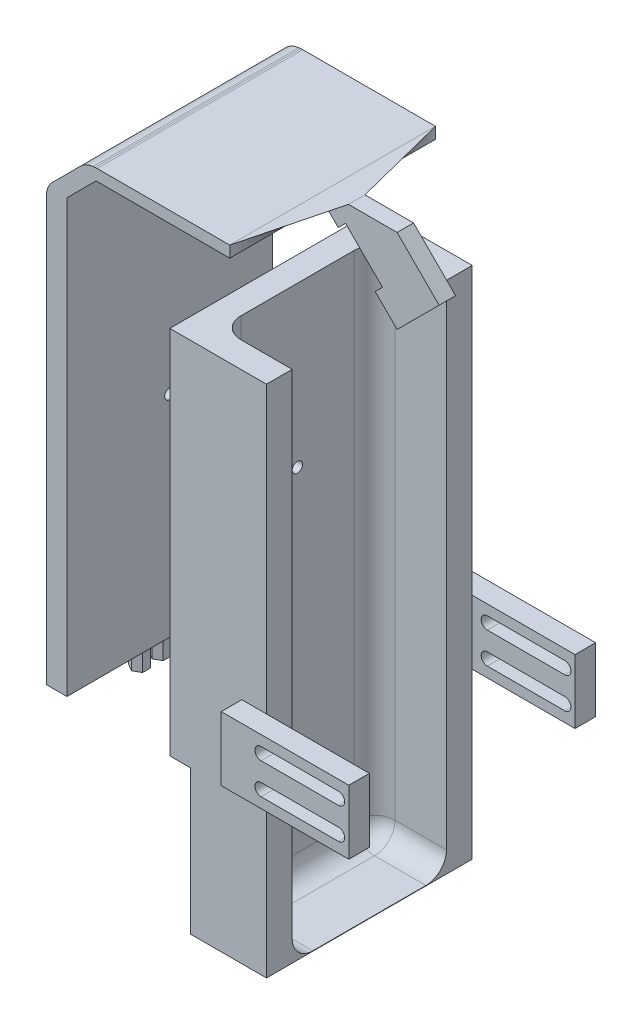
SolidWorks part; units mm, degrees
note: '?' marks a value the reader was unsure of.
ref_plane "Front Plane" through (0, 0, 0) normal (0, 0, 1) x (1, 0, 0)
ref_plane "Top Plane" through (0, 0, 0) normal (0, 1, 0) x (1, 0, 0)
ref_plane "Right Plane" through (0, 0, 0) normal (1, 0, 0) x (0, 0, -1)
sketch "Sketch1" plane through (0, 0, 0) normal (0, 1, 0) x (1, 0, 0)
  line L1 (0, 0) -> (25, 0)
  line L2 (0, 0) -> (0, 100)
  line L3 (0, 100) -> (25, 100)
  line L4 (25, 0) -> (25, 100)
  dimension "D1" = 100
  dimension "D2" = 25
extrude "Boss-Extrude1" add sketch "Sketch1" along normal blind 250
ref_plane "Plane1" through (35, 0, 0) normal (1, 0, 0) x (0, 0, -1)
ref_axis "Axis1" through (25, 250, 291.9882) along (0, 0, -1)?
ref_plane "Plane2" through (137.5, 137.5, 0) normal (-0.7071, -0.7071, 0) x (0, 0, -1)
sketch "Sketch5" plane through (0, 250, 0) normal (0, 1, 0) x (1, 0, 0)
  line L0 (0, 0) -> (-50, 0) construction
  line L2 (-50, 0) -> (-60, 0)
  line L3 (-50, 0) -> (-50, 100)
  line L4 (-50, 100) -> (-60, 100)
  line L5 (-60, 0) -> (-60, 100)
  dimension "D1" = 10
  dimension "D2" = 100
  dimension "D3" = 50
extrude "Boss-Extrude2" add sketch "Sketch5" against normal blind 250 and the other way blind 30 separate body
sketch "Sketch6" plane through (-60, 0, 0) normal (-1, 0, 0) x (0, 0, 1)
  line L0 (-100, 0) -> (-100, 175) construction
  line L1 (-100, 0) -> (-100, 280) construction
  line L2 (0, 0) -> (0, 280) construction
  line L3 (-100, 175) -> (0, 175) construction
  line L4 (-100, 175) -> (-100, 170) construction
  line L5 (-100, 170) -> (0, 170) construction
  line L6 (0, 175) -> (0, 170) construction
  line L7 (-50, 175) -> (-50, 170) construction
  circle A0 centre (-50, 172.5) radius 2.5
  dimension "D1" = 5
  dimension "D2" = 175
extrude "Cut-Extrude1" cut sketch "Sketch6" against normal blind 250
ref_plane "Plane3" through (115, 115, 0) normal (0.7071, 0.7071, 0) x (0, 0, -1)
sketch "Sketch7" plane through (115, 115, 0) normal (0.7071, 0.7071, 0) x (0, 0, -1)
  line L1 (0, 233.3452) -> (100, 233.3452)
  line L2 (0, 233.3452) -> (0, 240.4163)
  line L3 (0, 240.4163) -> (100, 240.4163)
  line L4 (100, 233.3452) -> (100, 240.4163)
extrude "Boss-Extrude3" add sketch "Sketch7" along normal blind 20 separate body
loft "Loft1" add section face at (-55, 280, -50) section face at (-52.5, 282.5, -50)
fillet "Fillet1" radius 10 1 edges
ref_plane "Plane4" through (-35.8579, 0, 0) normal (1, 0, 0) x (0, 0, -1)
sketch "Sketch8" plane through (-35.8579, 0, 0) normal (1, 0, 0) x (0, 0, -1)
  line L1 (100, 294.1421) -> (0, 294.1421)
  line L2 (100, 294.1421) -> (100, 299.6421)
  line L3 (100, 299.6421) -> (0, 299.6421)
  line L4 (0, 294.1421) -> (0, 299.6421)
  dimension "D1" = 5.5
  dimension "D2" = 100
extrude "Boss-Extrude4" add sketch "Sketch8" along normal blind 65 separate body
loft "Loft2" add section face at (-38.3579, 296.6421, -50) section face at (-35.8579, 296.8921, -50)
fillet "Fillet2" radius 10 2 edges
ref_plane "Plane5" through (-132.5, 132.5, 0) normal (0.7071, -0.7071, 0) x (0, 0, -1)
sketch "Sketch9" plane through (-132.5, 132.5, 0) normal (0.7071, -0.7071, 0) x (0, 0, -1)
  line L0 (0, 228.5965) -> (100, 228.5965) construction
  line L5 (46, 232.4856) -> (54, 232.4856) construction
  line L6 (46, 232.4856) -> (54, 232.4856)
  line L7 (46, 232.4856) -> (46, 228.5965)
  line L8 (46, 228.5965) -> (54, 228.5965)
  line L9 (54, 232.4856) -> (54, 228.5965)
  line L10 (100, 232.4856) -> (0, 232.4856) construction
  point P9 (50, 232.4856)
  dimension "D1" = 8
  dimension "D2" = 46
extrude "Boss-Extrude5" add sketch "Sketch9" along normal blind 50 separate body
sketch "Sketch11" plane through (161.6421, 161.6421, 0) normal (-0.7071, -0.7071, 0) x (0, 0, 1)
  line L0 (-46, 137.3833) -> (-46, 162.3833) construction
  line L1 (-46, 137.3833) -> (-46, 187.3833) construction
  line L2 (-54, 137.3833) -> (-54, 187.3833) construction
  line L3 (-46, 162.3833) -> (-54, 162.3833) construction
  line L4 (-46, 162.3833) -> (-46, 167.9142) construction
  line L5 (-46, 167.9142) -> (-54, 167.9142) construction
  line L6 (-54, 162.3833) -> (-54, 167.9142) construction
  line L7 (-50, 167.9142) -> (-50, 162.3833) construction
  line L8 (-54, 165.1488) -> (-46, 165.1488) construction
  line L10 (-62.7, 152.4488) -> (-37.3, 152.4488)
  line L11 (-62.7, 152.4488) -> (-62.7, 177.8488)
  line L12 (-62.7, 177.8488) -> (-37.3, 177.8488)
  line L13 (-37.3, 152.4488) -> (-37.3, 177.8488)
  line L14 (-62.7, 152.4488) -> (-37.3, 177.8488) construction
  line L15 (-62.7, 177.8488) -> (-37.3, 152.4488) construction
  point P14 (-50, 165.1488)
  dimension "D1" = 25.4
  dimension "D2" = 25.4
  dimension "D3" = 9.5345
sketch "Sketch12" plane through (-97.1447, 97.1447, 0) normal (0.7071, -0.7071, 0) x (0, 0, -1)
  line L2 (46, 232.4856) -> (54, 232.4856)
  line L3 (46, 232.4856) -> (46, 257.4856)
  line L4 (46, 257.4856) -> (54, 257.4856)
  line L5 (54, 232.4856) -> (54, 257.4856)
  dimension "D1" = 25
  dimension "D2" = 8
extrude "Boss-Extrude7" add sketch "Sketch12" against normal blind 50
extrude "Cut-Extrude4" cut sketch "Sketch11" against normal blind 5
sketch "Sketch14" plane through (35, 0, 0) normal (1, 0, 0) x (0, 0, -1)
  line L6 (100, 299.6421) -> (0, 299.6421) construction
  line L7 (54, 314.5698) -> (46, 314.5698)
  line L8 (54, 314.5698) -> (54, 299.6421)
  line L9 (54, 299.6421) -> (46, 299.6421)
  line L10 (46, 314.5698) -> (46, 299.6421)
  line L11 (54, 314.5698) -> (46, 314.5698) construction
  dimension "D1" = 8
extrude "Cut-Extrude6" cut sketch "Sketch14" along normal blind 80 and the other way blind 10
sketch "Sketch15" plane through (0, 0, 0) normal (0, 0, 1) x (1, 0, 0)
  line L1 (25, 0) -> (47, 0)
  line L2 (25, 0) -> (25, 250)
  line L3 (25, 250) -> (47, 250)
  line L4 (47, 0) -> (47, 250)
  dimension "D1" = 22
  dimension "D2" = 25
extrude "Boss-Extrude8" add sketch "Sketch15" against normal blind 100
sketch "Sketch16" plane through (47, 0, 0) normal (1, 0, 0) x (0, 0, -1)
  line L0 (0, 0) -> (100, 0) construction
  line L1 (12.5, 0) -> (87.5, 0) construction
  line L2 (100, 250) -> (0, 250) construction
  line L3 (12.5, 0) -> (87.5, 0)
  line L4 (12.5, 0) -> (12.5, 250)
  line L5 (12.5, 250) -> (87.5, 250)
  line L6 (87.5, 0) -> (87.5, 250)
  line L7 (0, 280) -> (0, 0) construction
  point P7 (50, 0)
  dimension "D1" = 12.5
extrude "Cut-Extrude7" cut sketch "Sketch16" against normal blind 35
fillet "Fillet4" radius 10 2 edges at (12, 125, -87.5) (12, 125, -12.5)
sketch "Sketch18" plane through (0, 0, -87.5) normal (0, 0, 1) x (1, 0, 0)
  line L1 (47, 0) -> (12, 0)
  line L2 (47, 0) -> (47, 0.2)
  line L3 (47, 0.2) -> (12, 0.2)
  line L4 (12, 0) -> (12, 0.2)
  dimension "D1" = 35
  dimension "D2" = 0.2
extrude "Boss-Extrude10" add sketch "Sketch18" along normal blind 75
fillet "Fillet5" radius 10 5 edges at (34.5, 0.2, -12.5) (14.9289, 0.2, -15.4289) (34.5, 0.2, -87.5) (14.9289, 0.2, -84.5711) (12, 0.2, -50)
fillet "Fillet6" radius 15 1 edges at (34.6421, 299.6421, -50)
surface "Surface-Loft1"
sketch "Sketch19" plane through (0, 0, 0) normal (0, 0, 1) x (1, 0, 0)
  line L0 (0, 0) -> (0, 80) construction
  line L1 (0, 250) -> (0, 0) construction
  line L2 (0, 80) -> (47, 80) construction
  line L3 (47, 0) -> (47, 250) construction
  line L4 (54.3576, 103.16) -> (92, 103.16) construction
  line L5 (47, 80) -> (97, 80)
  line L7 (47, 111.16) -> (97, 111.16)
  line L8 (97, 80) -> (97, 111.16)
  line L9 (54.3576, 106.16) -> (92, 106.16)
  line L10 (54.3576, 100.16) -> (92, 100.16)
  line L11 (54.3576, 88) -> (92, 88) construction
  line L12 (54.3576, 91) -> (92, 91)
  line L13 (54.3576, 85) -> (92, 85)
  line L14 (92, 106.16) -> (92, 111.16) construction
  line L15 (92, 106.16) -> (97, 111.16)
  line L16 (47, 111.16) -> (35, 111.16)
  line L17 (35, -55.0055) -> (35, 55.0055) construction
  line L18 (35, 111.16) -> (35, 80)
  line L19 (35, 80) -> (47, 80)
  arc A0 (54.3576, 106.16) -> (54.3576, 100.16) centre (54.3576, 103.16) ccw
  arc A1 (92, 100.16) -> (92, 106.16) centre (92, 103.16) ccw
  arc A2 (54.3576, 91) -> (54.3576, 85) centre (54.3576, 88) ccw
  arc A3 (92, 85) -> (92, 91) centre (92, 88) ccw
  point P13 (73.1788, 103.16)
  point P23 (73.1788, 88)
  dimension "D8" = 5
  dimension "D4" = 45
  dimension "D1" = 31.16
  dimension "D2" = 12
  dimension "D3" = 80
  dimension "D5" = 6
  dimension "D7" = 9.16
  dimension "D9" = 37.6424
  dimension "D10" = 50
  dimension "D6" = 2
extrude "Boss-Extrude11" add sketch "Sketch19" against normal blind 110 and the other way blind 10
sketch "Sketch20" plane through (0, 111.16, 0) normal (0, 1, 0) x (1, 0, 0)
  line L5 (97, -10) -> (97, 110) construction
  line L6 (47, 100) -> (97, 100)
  line L8 (47, 0) -> (97, 0)
  line L9 (97, 100) -> (97, 0)
  line L10 (22, 12.5) -> (47, 12.5) construction
  line L11 (34.5, 12.5) -> (47, 12.5)
  line L12 (34.5, 12.5) -> (34.5, 87.5)
  line L13 (34.5, 87.5) -> (47, 87.5)
  line L15 (47, 87.5) -> (35, 87.5) construction
  line L17 (47, 12.5) -> (47, 0)
  line L18 (47, 100) -> (47, 87.5)
  dimension "D1" = 50
  dimension "D2" = 100
extrude "Cut-Extrude8" cut sketch "Sketch20" against normal blind 100
sketch "Sketch21" plane through (0, 0, 0) normal (0, 0, 1) x (1, 0, 0)
  line L0 (0, 0) -> (0, 70) construction
  line L1 (0, 250) -> (0, 0) construction
  line L2 (0, 70) -> (10, 70) construction
  line L3 (0, 0) -> (47, 0) construction
  line L4 (0, 70) -> (10, 70)
  line L5 (0, 70) -> (0, 0)
  line L6 (0, 0) -> (10, 0)
  line L7 (10, 70) -> (10, 0)
  dimension "D1" = 10
  dimension "D2" = 70
extrude "Cut-Extrude9" cut sketch "Sketch21" against normal blind 100
sketch "Sketch23" plane through (0, 70, 0) normal (0, -1, 0) x (1, 0, 0)
  line L0 (10, 0) -> (0, 0) construction
  line L1 (5, -13.4637) -> (8, -11.7317)
  line L2 (8, -11.7317) -> (8, -8.2676)
  line L3 (8, -8.2676) -> (5, -6.5355)
  line L4 (5, -6.5355) -> (2, -8.2676)
  line L5 (2, -8.2676) -> (2, -11.7317)
  line L6 (2, -11.7317) -> (5, -13.4637)
  line L7 (5, -16.5355) -> (2, -18.2676)
  line L8 (5, -23.4637) -> (8, -21.7317)
  line L9 (8, -21.7317) -> (8, -18.2676)
  line L10 (8, -18.2676) -> (5, -16.5355)
  line L11 (2, -18.2676) -> (2, -21.7317)
  line L12 (2, -21.7317) -> (5, -23.4637)
  line L13 (5, -26.5355) -> (2, -28.2676)
  line L14 (5, -33.4637) -> (8, -31.7317)
  line L15 (8, -31.7317) -> (8, -28.2676)
  line L16 (8, -28.2676) -> (5, -26.5355)
  line L17 (2, -28.2676) -> (2, -31.7317)
  line L18 (2, -31.7317) -> (5, -33.4637)
  line L19 (5, -36.5355) -> (2, -38.2676)
  line L20 (5, -43.4637) -> (8, -41.7317)
  line L21 (8, -41.7317) -> (8, -38.2676)
  line L22 (8, -38.2676) -> (5, -36.5355)
  line L23 (2, -38.2676) -> (2, -41.7317)
  line L24 (2, -41.7317) -> (5, -43.4637)
  line L25 (5, -46.5355) -> (2, -48.2676)
  line L26 (5, -53.4637) -> (8, -51.7317)
  line L27 (8, -51.7317) -> (8, -48.2676)
  line L28 (8, -48.2676) -> (5, -46.5355)
  line L29 (2, -48.2676) -> (2, -51.7317)
  line L30 (2, -51.7317) -> (5, -53.4637)
  line L31 (5, -56.5355) -> (2, -58.2676)
  line L32 (5, -63.4637) -> (8, -61.7317)
  line L33 (8, -61.7317) -> (8, -58.2676)
  line L34 (8, -58.2676) -> (5, -56.5355)
  line L35 (2, -58.2676) -> (2, -61.7317)
  line L36 (2, -61.7317) -> (5, -63.4637)
  line L37 (5, -66.5355) -> (2, -68.2676)
  line L38 (5, -73.4637) -> (8, -71.7317)
  line L39 (8, -71.7317) -> (8, -68.2676)
  line L40 (8, -68.2676) -> (5, -66.5355)
  line L41 (2, -68.2676) -> (2, -71.7317)
  line L42 (2, -71.7317) -> (5, -73.4637)
  line L43 (5, -76.5355) -> (2, -78.2676)
  line L44 (5, -83.4637) -> (8, -81.7317)
  line L45 (8, -81.7317) -> (8, -78.2676)
  line L46 (8, -78.2676) -> (5, -76.5355)
  line L47 (2, -78.2676) -> (2, -81.7317)
  line L48 (2, -81.7317) -> (5, -83.4637)
  line L49 (5, -86.5355) -> (2, -88.2676)
  line L50 (5, -93.4637) -> (8, -91.7317)
  line L51 (8, -91.7317) -> (8, -88.2676)
  line L52 (8, -88.2676) -> (5, -86.5355)
  line L53 (2, -88.2676) -> (2, -91.7317)
  line L54 (2, -91.7317) -> (5, -93.4637)
  line L56 (0, -100) -> (0, 0) construction
  circle A0 centre (5, -9.9996) radius 3.4641 construction
  dimension "D1" = 6.9282
  dimension "D2" = 6.5355
  dimension "D4" = 2
  dimension "D5" = 3.0718
  dimension "D3" = 9
extrude "Boss-Extrude12" add sketch "Sketch23" along normal blind 10
sketch "Sketch24" plane through (0, 0, 0) normal (0, 0, 1) x (1, 0, 0)
  line L0 (-50, 280) -> (-50, 0) construction
  line L1 (-60, 0) -> (-50, 0)
  line L2 (-60, 0) -> (-60, 70)
  line L3 (-60, 70) -> (-50, 70)
  line L4 (-50, 0) -> (-50, 70)
  dimension "D1" = 70
extrude "Cut-Extrude10" cut sketch "Sketch24" against normal blind 100
sketch "Sketch25" plane through (0, 70, 0) normal (0, -1, 0) x (1, 0, 0)
  line L0 (-50, 0) -> (-60, 0) construction
  line L1 (-55.0991, -14.3895) -> (-51.6982, -12.426)
  line L2 (-51.6982, -12.426) -> (-51.6982, -8.499)
  line L3 (-51.6982, -8.499) -> (-55.0991, -6.5355)
  line L4 (-55.0991, -6.5355) -> (-58.5, -8.499)
  line L5 (-58.5, -8.499) -> (-58.5, -12.426)
  line L6 (-58.5, -12.426) -> (-55.0991, -14.3895)
  line L7 (-60, -100) -> (-60, 0) construction
  line L8 (-55.0991, -24.3895) -> (-51.6982, -22.426)
  line L9 (-51.6982, -22.426) -> (-51.6982, -18.499)
  line L10 (-51.6982, -18.499) -> (-55.0991, -16.5355)
  line L11 (-55.0991, -16.5355) -> (-58.5, -18.499)
  line L12 (-58.5, -18.499) -> (-58.5, -22.426)
  line L13 (-58.5, -22.426) -> (-55.0991, -24.3895)
  line L14 (-55.0991, -34.3895) -> (-51.6982, -32.426)
  line L15 (-51.6982, -32.426) -> (-51.6982, -28.499)
  line L16 (-51.6982, -28.499) -> (-55.0991, -26.5355)
  line L17 (-55.0991, -26.5355) -> (-58.5, -28.499)
  line L18 (-58.5, -28.499) -> (-58.5, -32.426)
  line L19 (-58.5, -32.426) -> (-55.0991, -34.3895)
  line L20 (-55.0991, -44.3895) -> (-51.6982, -42.426)
  line L21 (-51.6982, -42.426) -> (-51.6982, -38.499)
  line L22 (-51.6982, -38.499) -> (-55.0991, -36.5355)
  line L23 (-55.0991, -36.5355) -> (-58.5, -38.499)
  line L24 (-58.5, -38.499) -> (-58.5, -42.426)
  line L25 (-58.5, -42.426) -> (-55.0991, -44.3895)
  line L26 (-55.0991, -54.3895) -> (-51.6982, -52.426)
  line L27 (-51.6982, -52.426) -> (-51.6982, -48.499)
  line L28 (-51.6982, -48.499) -> (-55.0991, -46.5355)
  line L29 (-55.0991, -46.5355) -> (-58.5, -48.499)
  line L30 (-58.5, -48.499) -> (-58.5, -52.426)
  line L31 (-58.5, -52.426) -> (-55.0991, -54.3895)
  line L32 (-55.0991, -64.3895) -> (-51.6982, -62.426)
  line L33 (-51.6982, -62.426) -> (-51.6982, -58.499)
  line L34 (-51.6982, -58.499) -> (-55.0991, -56.5355)
  line L35 (-55.0991, -56.5355) -> (-58.5, -58.499)
  line L36 (-58.5, -58.499) -> (-58.5, -62.426)
  line L37 (-58.5, -62.426) -> (-55.0991, -64.3895)
  line L38 (-55.0991, -74.3895) -> (-51.6982, -72.426)
  line L39 (-51.6982, -72.426) -> (-51.6982, -68.499)
  line L40 (-51.6982, -68.499) -> (-55.0991, -66.5355)
  line L41 (-55.0991, -66.5355) -> (-58.5, -68.499)
  line L42 (-58.5, -68.499) -> (-58.5, -72.426)
  line L43 (-58.5, -72.426) -> (-55.0991, -74.3895)
  line L44 (-55.0991, -84.3895) -> (-51.6982, -82.426)
  line L45 (-51.6982, -82.426) -> (-51.6982, -78.499)
  line L46 (-51.6982, -78.499) -> (-55.0991, -76.5355)
  line L47 (-55.0991, -76.5355) -> (-58.5, -78.499)
  line L48 (-58.5, -78.499) -> (-58.5, -82.426)
  line L49 (-58.5, -82.426) -> (-55.0991, -84.3895)
  line L50 (-55.0991, -94.3895) -> (-51.6982, -92.426)
  line L51 (-51.6982, -92.426) -> (-51.6982, -88.499)
  line L52 (-51.6982, -88.499) -> (-55.0991, -86.5355)
  line L53 (-55.0991, -86.5355) -> (-58.5, -88.499)
  line L54 (-58.5, -88.499) -> (-58.5, -92.426)
  line L55 (-58.5, -92.426) -> (-55.0991, -94.3895)
  circle A0 centre (-55.0991, -10.4625) radius 3.927 construction
  dimension "D4" = 7.854
  dimension "D1" = 6.5355
  dimension "D2" = 1.5
  dimension "D5" = 2.146
  dimension "D3" = 9
extrude "Boss-Extrude13" add sketch "Sketch25" along normal blind 10
sketch "Sketch26" plane through (0, 60, 0) normal (0, -1, 0) x (1, 0, 0)
  line L0 (-50, 0) -> (-50, -100) construction
  line L1 (-60, 0) -> (-50, 0)
  line L2 (-60, 0) -> (-60, -34.8814)
  line L3 (-60, -34.8814) -> (-50, -34.8814)
  line L4 (-50, 0) -> (-50, -34.8814)
  line L6 (-60, -100) -> (-50, -100)
  line L7 (-60, -100) -> (-60, -65.3157)
  line L8 (-60, -65.3157) -> (-50, -65.3157)
  line L9 (-50, -100) -> (-50, -65.3157)
  dimension "D1" = 34.8814
  dimension "D2" = 30.9262
extrude "Cut-Extrude11" cut sketch "Sketch26" against normal blind 10
